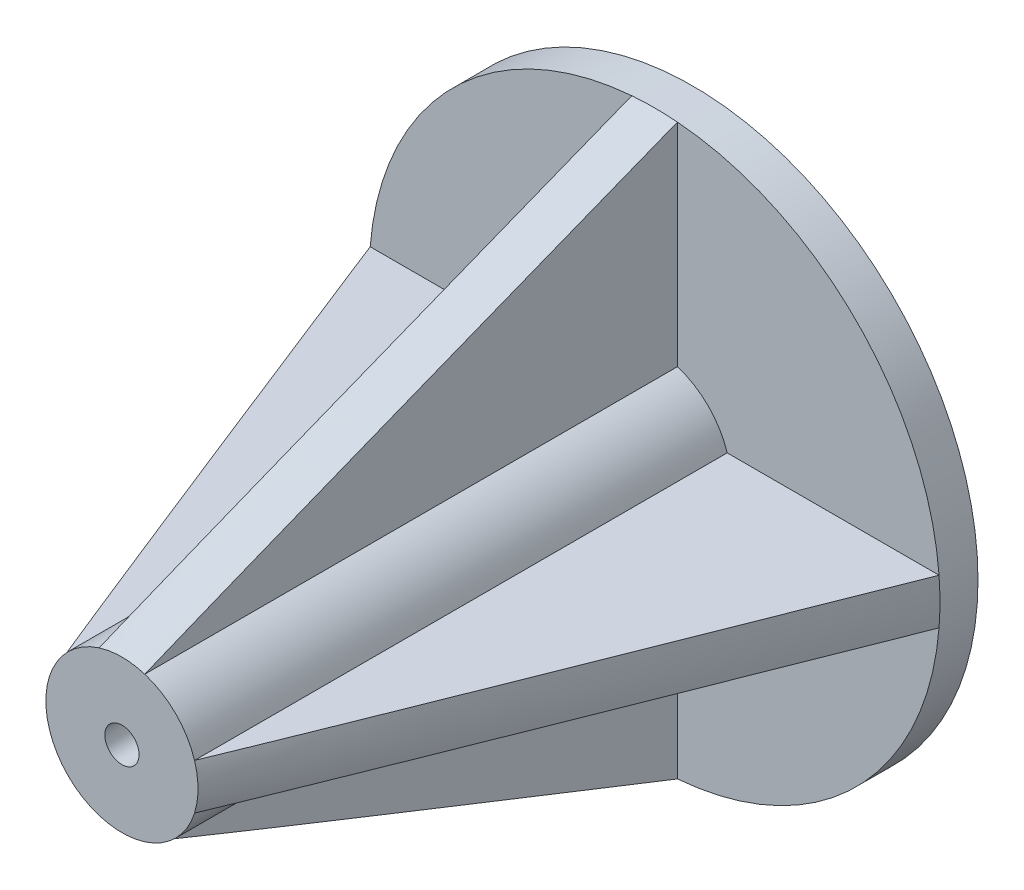
SolidWorks part; units mm, degrees
ref_plane "Front Plane" through (0, 0, 0) normal (0, 0, 1) x (1, 0, 0)
ref_plane "Top Plane" through (0, 0, 0) normal (0, 1, 0) x (1, 0, 0)
ref_plane "Right Plane" through (0, 0, 0) normal (1, 0, 0) x (0, 0, -1)
sketch "Sketch1" plane through (0, 0, 0) normal (0, 0, 1) x (1, 0, 0)
  circle A0 centre (0, 0) radius 15
  circle A1 centre (0, 0) radius 4
  circle A2 centre (0, 0) radius 0.9
  dimension "D1" = 1.8
  dimension "D2" = 8
  dimension "D3" = 30
extrude "Boss-Extrude1" add sketch "Sketch1" along normal blind 2 contours A0 | A2
extrude "Boss-Extrude2" add sketch "Sketch1<3>" along normal blind 30 contours A1 | A2
sketch "Sketch1<3>" plane through (0, 0, 0) normal (0, 0, 1) x (1, 0, 0) same geometry as "Sketch1"
sketch "Sketch2" plane through (0, 0, 2) normal (0, 0, 1) x (1, 0, 0)
  line L0 (-1.2, 14.9519) -> (-1.2, 3.8158)
  line L1 (1.2, 14.9519) -> (1.2, 3.8158)
  line L2 (14.9519, -1.2) -> (3.8158, -1.2)
  line L3 (14.9519, 1.2) -> (3.8158, 1.2)
  line L4 (-1.2, -14.9519) -> (-1.2, -3.8158)
  line L5 (1.2, -14.9519) -> (1.2, -3.8158)
  line L6 (-14.9519, 1.2) -> (-3.8158, 1.2)
  line L7 (-14.9519, -1.2) -> (-3.8158, -1.2)
  circle A0 centre (0, 0) radius 15 construction
  circle A1 centre (0, 0) radius 4 construction
  circle A2 centre (0, 0) radius 4 construction
  circle A3 centre (0, 0) radius 4
  circle A4 centre (0, 0) radius 15
  point P27 (0, 0)
  circle M4 centre (0, 0) radius 15
  circle M5 centre (0, 0) radius 4
  dimension "D1" = 2.4
  dimension "D2" = 4
extrude "Boss-Extrude3" add sketch "Sketch2" along normal up to surface (28 mm away) contours L1 L0 M4 M5 | L3 L2 M4 M5 | L5 L4 M4 M5 | L7 L6 M4 M5 region at (0, 9.4614, 2) region at (-9.4614, 0, 2) region at (9.4614, 0, 2) region at (0, -9.4614, 2) up to face at (4, 0, 30)
chamfer "Chamfer1" distance 28 distance2 11 4 edges at (-15, 0, 30) (0, 15, 30) (15, 0, 30) (0, -15, 30) first distance on face at (0, 0, 16)
